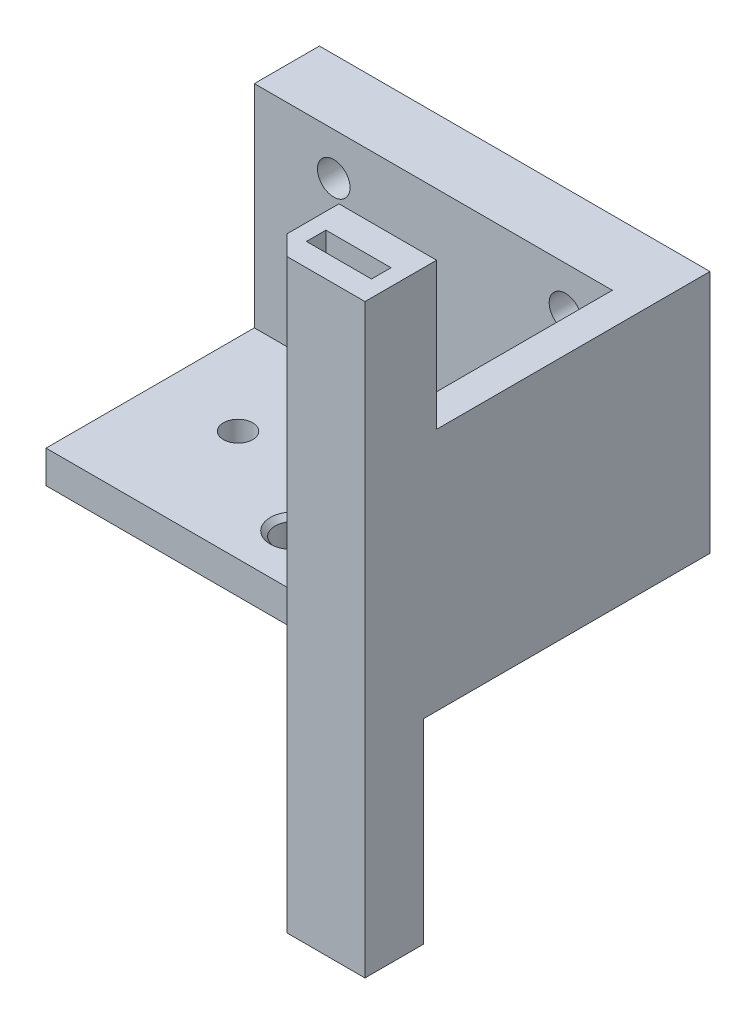
SolidWorks part; units mm, degrees
material "PET"
ref_plane "Front Plane" through (0, 0, 0) normal (0, 0, 1) x (1, 0, 0)
ref_plane "Top Plane" through (0, 0, 0) normal (0, 1, 0) x (1, 0, 0)
ref_plane "Right Plane" through (0, 0, 0) normal (1, 0, 0) x (0, 0, -1)
sketch "Sketch1" plane through (0, 0, 0) normal (0, 1, 0) x (1, 0, 0)
  line L0 (-30, 15) -> (30, 15) construction
  line L2 (-30, 0) -> (-30, 40)
  line L3 (-30, 40) -> (30, 40)
  line L4 (30, 0) -> (30, 40)
  line L5 (0, 0) -> (30, 40) construction
  line L6 (-30, 40) -> (0, 0) construction
  line L7 (-30, 22.5) -> (30, 22.5) construction
  line L8 (-30, 0) -> (-30, -2)
  line L11 (-30, -2) -> (30, -2)
  line L12 (30, -2) -> (30, 0)
  line L13 (-30, 0) -> (30, 0) construction
  line L14 (0, 0) -> (0, 27.8808) construction
  circle A0 centre (-12.5, 22.5) radius 2.8
  circle A1 centre (12.5, 22.5) radius 2.8
  circle A3 centre (-17.5, 15) radius 2.25
  circle A4 centre (17.5, 15) radius 2.25
  circle A6 centre (0, 6) radius 2.8
  point P0 (0, 0)
  dimension "D6" = 5.6
  dimension "D7" = 5.6
  dimension "D8" = 4.5
  dimension "D9" = 4.5
  dimension "D5" = 5.6
  dimension "D2" = 60
  dimension "D4" = 17.5
  dimension "D10" = 12.5
  dimension "D11" = 12.5
  dimension "D12" = 25
  dimension "D17" = 40
  dimension "D18" = 30
  dimension "D20" = 17.5
  dimension "D21" = 17.5
  dimension "D3" = 2
  dimension "D13" = 6
extrude "Boss-Extrude1" add sketch "Sketch1" along normal blind 5
sketch "Sketch3" plane through (0, 5, 0) normal (0, 1, 0) x (1, 0, 0)
  line L2 (-30, 40) -> (-30, 30)
  line L3 (-30, 30) -> (30, 30)
  line L5 (30, 40) -> (-30, 40)
  line L6 (30, 40) -> (30, 30)
  dimension "D2" = 10
extrude "Boss-Extrude3" add sketch "Sketch3" along normal blind 32.5
sketch "Sketch4" plane through (0, 0, -40) normal (0, 0, -1) x (-1, 0, 0)
  line L0 (-30, 0) -> (30, 0) construction
  line L2 (-17.8, 31) -> (17.8, 31) construction
  circle A0 centre (-17.8, 31) radius 2.5
  circle A1 centre (17.8, 31) radius 2.5
  dimension "D3" = 5
  dimension "D4" = 5
  dimension "D1" = 17.8
  dimension "D2" = 35.6
  dimension "D5" = 31
extrude "Cut-Extrude1" cut sketch "Sketch4" against normal through all
chamfer "Chamfer1" distance 0.75 angle 45 3 edges at (-12.5, 5, -19.7) (12.5, 5, -19.7) (0, 5, -3.2)
sketch "Sketch5" plane through (0, 0, 0) normal (0, -1, 0) x (1, 0, 0)
  line L0 (18, 13) -> (15, 10)
  line L1 (30, 2) -> (15, 2)
  line L2 (30, 2) -> (30, 13)
  line L3 (30, 13) -> (18, 13)
  line L6 (15, 2) -> (15, 10)
  line L7 (27.5, 9.5) -> (17.5, 9.5)
  line L8 (27.5, 9.5) -> (27.5, 6.5)
  line L9 (27.5, 6.5) -> (17.5, 6.5)
  line L10 (17.5, 9.5) -> (17.5, 6.5)
  dimension "D1" = 11
  dimension "D2" = 12
  dimension "D3" = 10
  dimension "D4" = 2.5
  dimension "D5" = 3
  dimension "D6" = 4.5
  dimension "D7" = 15
  dimension "D8" = 135
extrude "Boss-Extrude4" add sketch "Sketch5" along normal blind 30 and the other way blind 60
chamfer "Chamfer2" distance 10 angle 45 1 edges at (22.5, 5, 2)
chamfer "Chamfer3" distance 5 angle 45 2 edges at (15, 5, -3) (15, 2.5, 2)
sketch "Sketch7" plane through (30, 0, 0) normal (1, 0, 0) x (0, 0, -1)
  line L0 (-2, -30) -> (-13, -30) construction
  line L1 (-2, 0) -> (-4, 0)
  line L2 (-2, 0) -> (-2, -30)
  line L3 (-2, -30) -> (-4, -30)
  line L4 (-4, 0) -> (-4, -30)
  dimension "D1" = 2
extrude "Cut-Extrude2" cut sketch "Sketch7" against normal through all
sketch "Sketch8" plane through (30, 0, 0) normal (1, 0, 0) x (0, 0, -1)
  line L0 (30, 37.5) -> (-2, 37.5)
  line L1 (-2, 60) -> (-2, 15) construction
  line L2 (-2, 37.5) -> (-2, 15)
  line L3 (-2, 15) -> (8, 5)
  line L4 (8, 5) -> (30, 5)
  line L5 (30, 5) -> (30, 37.5)
extrude "Boss-Extrude5" add sketch "Sketch8" against normal blind 5
equation "\"D18@Sketch1\"=\"D2@Sketch1\"/2"
equation "\"D1@Sketch4\"=\"D2@Sketch4\"/2"
